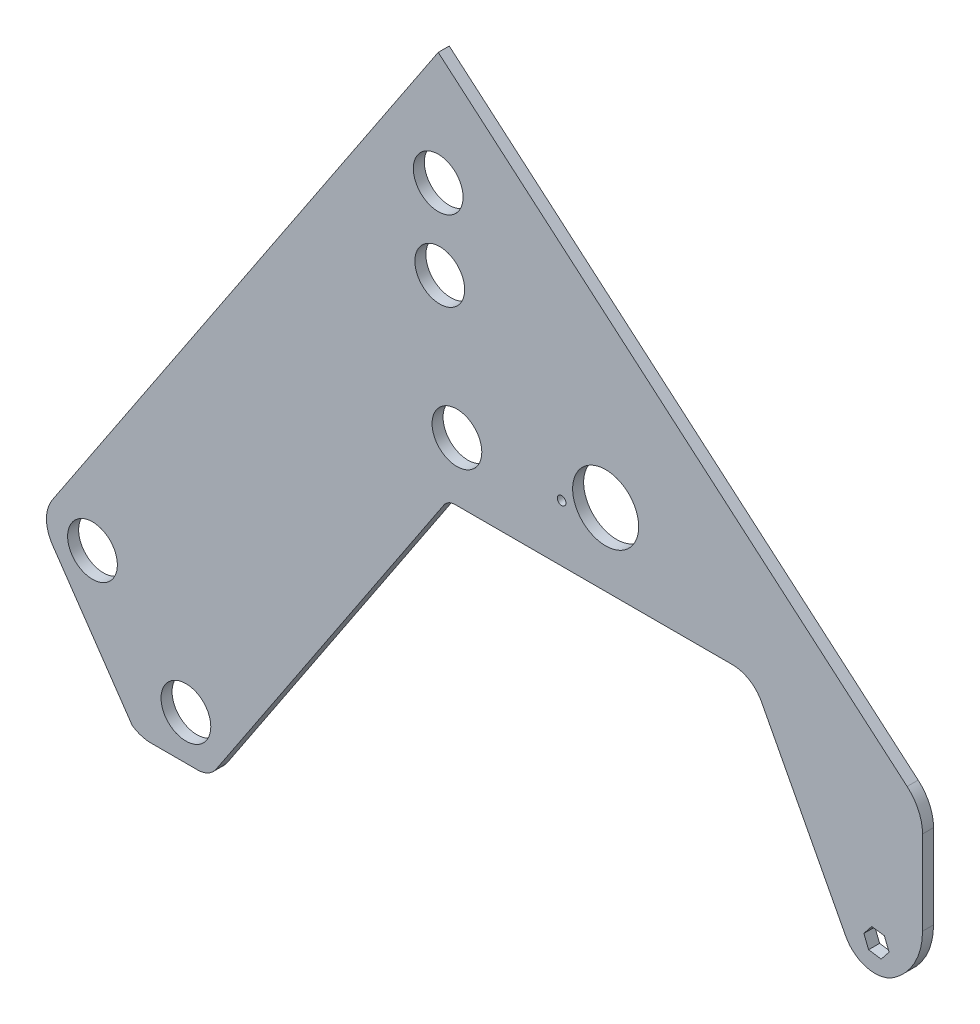
SolidWorks part; units mm, degrees
other "Markup1"
sketch "Sketch1" plane through (-441.7893, 331.8239, 6.35) normal (-0.0431, 0.0102, 0.999) x (0.9985, 0.0354, 0.0427)
sketch "Sketch2" plane through (-413.6701, 343.933, 6.35) normal (-0.0431, 0.0102, 0.999) x (0.9985, 0.0354, 0.0427)
ref_plane "Front Plane" through (0, 0, 0) normal (0, 0, 1) x (1, 0, 0)
ref_plane "Top Plane" through (0, 0, 0) normal (0, 1, 0) x (1, 0, 0)
ref_plane "Right Plane" through (0, 0, 0) normal (1, 0, 0) x (0, 0, -1)
sketch "Model" plane through (0, 0, 0) normal (0, 0, 1) x (1, 0, 0)
  line L1 (-195.5505, 132.3671) -> (-35.622, 132.3671)
  line L3 (-333.3655, -68.8016) -> (-201.8963, 128.9655)
  line L4 (-205.222, 353.3682) -> (-427.816, 18.5234)
  line L5 (-427.6641, -3.9626) -> (-381.6691, -71.1644)
  line L6 (-18.7476, 122.1576) -> (29.8348, 29.425)
  line L13 (54.8115, 33.9279) -> (52.1037, 40.742)
  line L14 (52.1037, 40.742) -> (44.8487, 41.804)
  line L15 (44.8487, 41.804) -> (40.3014, 36.0519)
  line L16 (40.3014, 36.0519) -> (43.0092, 29.2379)
  line L17 (43.0092, 29.2379) -> (50.2643, 28.1759)
  line L18 (50.2643, 28.1759) -> (54.8115, 33.9279)
  line L19 (-370.9433, -74.4708) -> (-343.9418, -74.4708)
  line L20 (-862.2578, -102.4108) -> (378.8652, -102.4108) construction
  line L21 (-350.7494, -49.0708) -> (-350.7494, 134.4536) construction
  line L22 (-404.6309, 4.8107) -> (-350.7494, -49.0708) construction
  line L23 (74.1137, 54.0296) -> (74.1137, 102.6061)
  line L24 (-205.222, 353.3682) -> (65.2294, 121.9036)
  circle A3 centre (-134.0441, 114.3) radius 2.4892
  arc A6 (-195.5505, 132.3671) -> (-201.8963, 128.9655) centre (-195.5505, 124.7471) ccw
  circle A9 centre (-350.7494, -49.0708) radius 14.351
  circle A10 centre (-404.6309, 4.8107) radius 14.351
  circle A12 centre (-194.434, 166.2337) radius 14.351
  circle A15 centre (-108.6441, 174.1898) radius 19.05
  circle A21 centre (-134.0441, 165.1) radius 2.4892
  circle A22 centre (-204.3285, 242.4337) radius 14.351
  circle A23 centre (-205.222, 288.1537) radius 14.351
  circle A24 centre (47.5565, 34.9899) radius 6.35 construction
  arc A27 (74.1137, 54.0296) -> (57.4048, 22.5013) centre (36.0137, 54.0296) cw
  arc A29 (-427.6641, -3.9626) -> (-427.816, 18.5234) centre (-411.0728, 7.393) cw
  arc A31 (-343.9418, -74.4708) -> (-333.3655, -68.8016) centre (-343.9418, -61.7708) ccw
  arc A32 (-370.9433, -74.4708) -> (-381.6691, -71.1644) centre (-370.9433, -55.4208) cw
  arc A33 (74.1137, 102.6061) -> (65.2294, 121.9036) centre (48.7137, 102.6061) ccw
  arc A34 (29.8348, 29.425) -> (57.4048, 22.5013) centre (46.7093, 38.2655) ccw
  arc A35 (-35.622, 132.3671) -> (-18.7476, 122.1576) centre (-35.622, 113.3171) cw
  point P34 (36.8996, 15.9399)
  point P41 (-24.0963, 132.3671)
  dimension "D2" = 76.2
  dimension "D3" = 25.4
  dimension "D4" = 19.05
  dimension "D5" = 7.62
  dimension "D6" = 124.389
  dimension "D1" = 177.8
  dimension "D7" = 12.7
  dimension "D8" = 76.2
  dimension "D11" = 127
  dimension "D12" = 27.94
  dimension "D21" = 109.4608
  dimension "D13" = 12.7
  dimension "D16" = 19.05
  dimension "D23" = 19.05
  dimension "D24" = 19.05
  dimension "D9" = 25.4
  dimension "D10" = 76.2
  dimension "D14" = 45.72
  dimension "D15" = 33.8667
  dimension "D17" = 310.7825
  dimension "D18" = 266.065
  dimension "D19" = 41.8228
  dimension "D20" = 45
  dimension "D22" = 25.4
extrude "Boss-Extrude1" add sketch "Model" along normal blind 6.35 contours L5 L3 L1 L6 L4 A23 A22 A21 A3 A9 A10 A12 A15 region at (-203.3276, 138.7322, 0)
